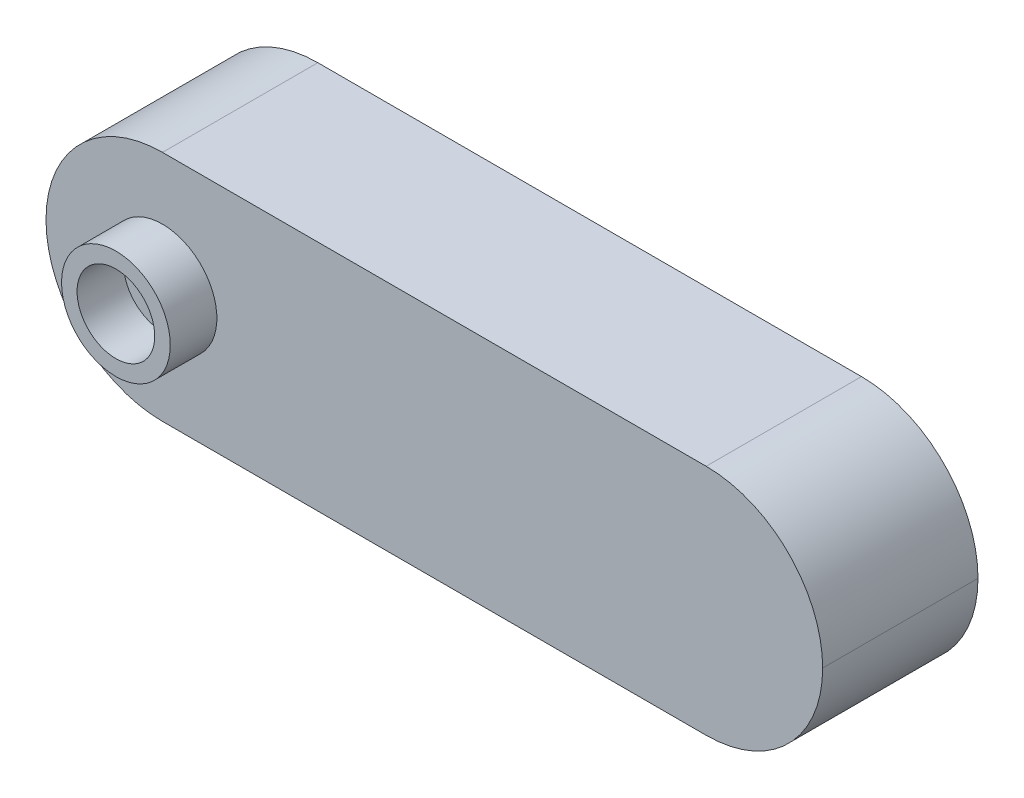
SolidWorks part; units mm, degrees
ref_plane "Front Plane" through (0, 0, 0) normal (0, 0, 1) x (1, 0, 0)
ref_plane "Top Plane" through (0, 0, 0) normal (0, 1, 0) x (1, 0, 0)
ref_plane "Right Plane" through (0, 0, 0) normal (1, 0, 0) x (0, 0, -1)
other "Configuration Table"
sketch "Sketch1" plane through (0, 0, 0) normal (0, 0, 1) x (1, 0, 0)
  line L5 (0, 0) -> (50, 0)
  line L6 (0, 0) -> (0, 15)
  line L7 (0, 15) -> (50, 15)
  line L8 (50, 0) -> (50, 15)
  dimension "D1" = 50
  dimension "D2" = 15
extrude "Boss-Extrude1" add sketch "Sketch1" along normal blind 10
fillet "Fillet1" radius 7.5 4 edges at (50, 0, 5) (50, 15, 5) (0, 0, 5) (0, 15, 5)
sketch "Sketch2" plane through (0, 0, 10) normal (0, 0, 1) x (1, 0, 0)
  circle A0 centre (7.5, 7.5) radius 3.5
  circle A1 centre (7.5, 7.5) radius 2.5
  dimension "D1" = 5
  dimension "D2" = 7
extrude "Boss-Extrude2" add sketch "Sketch2" along normal blind 3
